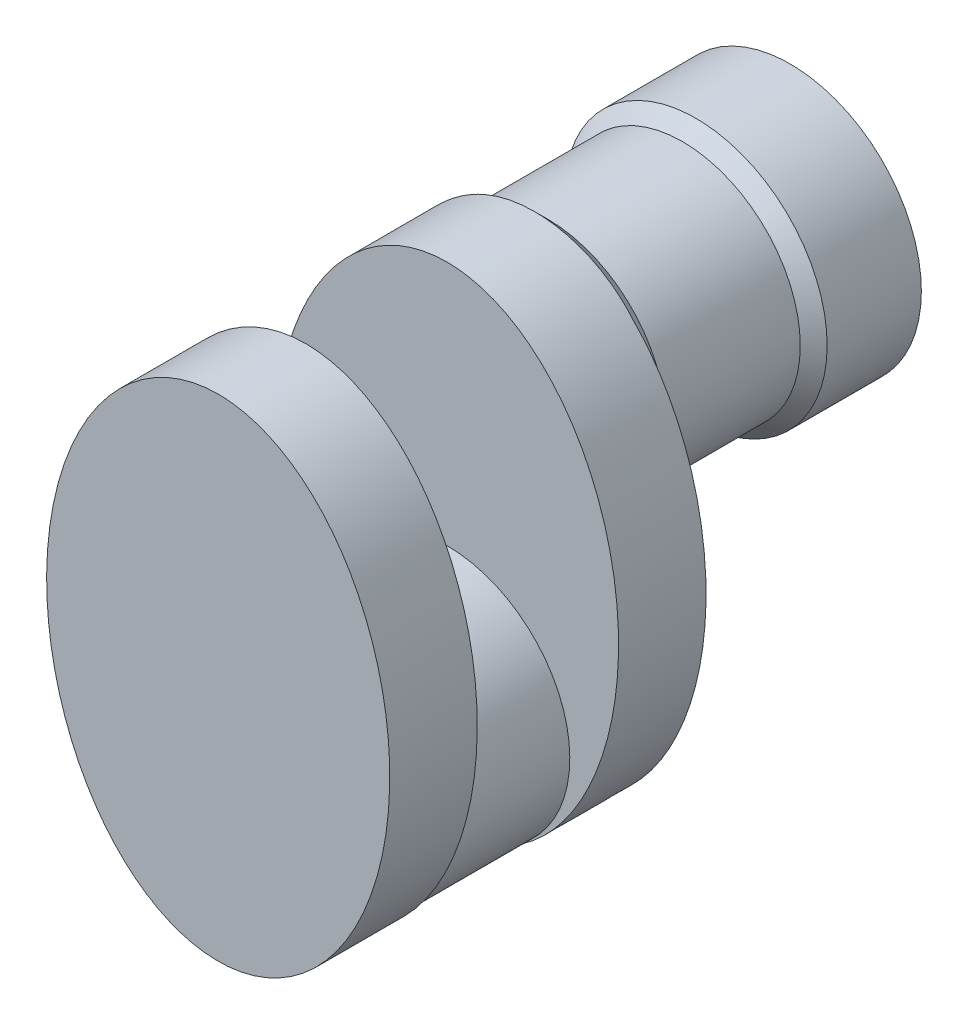
SolidWorks part; units mm, degrees
ref_plane "Front Plane" through (0, 0, 0) normal (0, 0, 1) x (1, 0, 0)
ref_plane "Top Plane" through (0, 0, 0) normal (0, 1, 0) x (1, 0, 0)
ref_plane "Right Plane" through (0, 0, 0) normal (1, 0, 0) x (0, 0, -1)
sketch "Sketch1" plane through (0, 0, 0) normal (0, 0, 1) x (1, 0, 0)
  circle A0 centre (0, 0) radius 19.5
  dimension "D1" = 39
extrude "Boss-Extrude2" add sketch "Sketch1" along normal blind 14
sketch "Sketch3" plane through (0, 0, 0) normal (0, 0, 1) x (1, 0, 0)
  circle A0 centre (0, 0) radius 17.5
  dimension "D1" = 35
extrude "Boss-Extrude3" add sketch "Sketch3" along normal blind 24 from surface starting at face at (19.5, 0, 14)
sketch "Sketch4" plane through (0, 0, 0) normal (0, 0, 1) x (1, 0, 0)
  line L0 (0, 0) -> (-38.5305, 0) construction
  line L1 (-38.5305, 0) -> (-38.5305, -17) construction
  line L2 (-38.5305, -17) -> (1.014, -17) construction
  line L3 (1.014, -17) -> (1.014, 1.1022) construction
  line L4 (1.014, 1.1022) -> (1.014, 17) construction
  line L5 (1.014, 17) -> (-38.5305, 17) construction
  line L6 (-38.5305, 17) -> (-38.5305, 0) construction
  circle A0 centre (0, 0) radius 19.5 construction
  ellipse E0 centre (0, -17) end of major axis (0, 19.5) minor radius 25.5
  dimension "D1" = 17
  dimension "D2" = 17
  dimension "D3" = 51
extrude "Boss-Extrude5" add sketch "Sketch4" along normal blind 13 from surface starting at face at (17.5, 0, 38)
chamfer "Chamfer2" distance 2 angle 45 1 edges at (17.5, 0, 38)
chamfer "Chamfer3" distance 2 angle 45 1 edges at (17.5, 0, 14)
sketch "Sketch6" plane through (0, 0, 51) normal (0, 0, 1) x (1, 0, 0)
  line L0 (0, 0) -> (0, -63.811) construction
  line L1 (0, 0) -> (-58.6322, 0) construction
  line L2 (0, -17) -> (-58.6322, -17) construction
  line L3 (0, -53.5) -> (-58.6322, -53.5) construction
  line L4 (0, -35.25) -> (-58.6322, -35.25) construction
  circle A2 centre (0, -35.25) radius 18.25
  spline S0 degree 3 poles (0, 19.5) (-51, 19.5) (-51, -53.5) (0, -53.5) (51, -53.5) (51, 19.5) (0, 19.5) (-51, 19.5) (-51, -53.5) knots -0.5 0 0 0 0.5 0.5 0.5 1 1 1 1.5 1.5 1.5 weights 1 0.333333 0.333333 1 0.333333 0.333333 1 0.333333 0.333333 only from (0, 19.5) to (0, 19.5) construction
  dimension "D1" = 17
  dimension "D2" = 18.25
  dimension "D3" = 18.25
extrude "Boss-Extrude6" add sketch "Sketch6" along normal blind 21
sketch "Sketch7" plane through (0, 0, 72) normal (0, 0, 1) x (1, 0, 0)
  arc A0 (7.6899, -51.8008) -> (-7.6899, -51.8008) centre (0, -35.25) ccw construction
  ellipse E0 centre (0, -17) end of major axis (0, -53.5) minor radius 25.5
  spline S0 degree 3 poles (7.6899, -51.8008) (48.3582, -33.3891) (34.8568, 19.5) (0, 19.5) (-34.8568, 19.5) (-48.3582, -33.3891) (-7.6899, -51.8008) knots 0.566865 0.566865 0.566865 0.566865 1 1 1 1.433135 1.433135 1.433135 1.433135 weights 0.768306 0.345256 0.422487 1 0.422487 0.345256 0.768306 construction
extrude "Boss-Extrude7" add sketch "Sketch7" along normal blind 13
sketch "Sketch8" plane through (0, 0, 85) normal (0, 0, 1) x (1, 0, 0)
  line L0 (0, -17) -> (-48.8349, -17) construction
  line L1 (-48.8349, -17) -> (-48.8349, -53.5) construction
  line L2 (-48.8349, -53.5) -> (0, -53.5) construction
  line L3 (0, -53.5) -> (0, -17) construction
  line L4 (0, -17) -> (0, 19.5) construction
  line L5 (0, 19.5) -> (-48.8349, 19.5) construction
  line L6 (-48.8349, 19.5) -> (-48.8349, -17) construction
  line L7 (-48.8349, 1.25) -> (0, 1.25) construction
